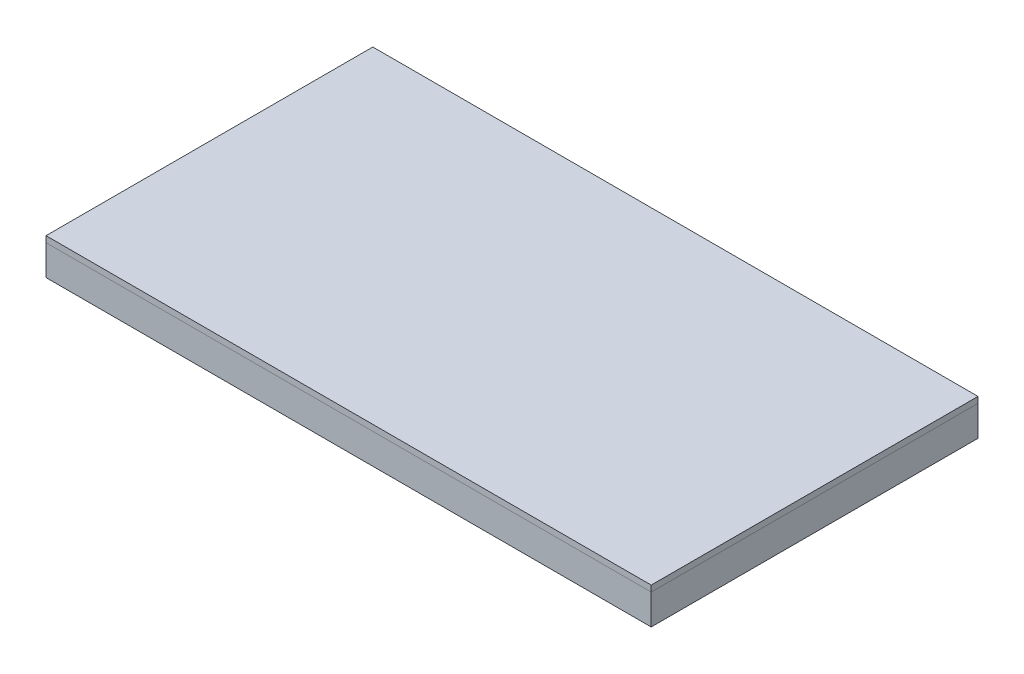
SolidWorks part; units mm, degrees
ref_plane "Front Plane" through (0, 0, 0) normal (0, 0, 1) x (1, 0, 0)
ref_plane "Top Plane" through (0, 0, 0) normal (0, 1, 0) x (1, 0, 0)
ref_plane "Right Plane" through (0, 0, 0) normal (1, 0, 0) x (0, 0, -1)
sketch "Sketch1" plane through (0, 0, 0) normal (0, 1, 0) x (1, 0, 0)
  line L1 (-500, -270) -> (500, -270)
  line L2 (-500, -270) -> (-500, 270)
  line L3 (-500, 270) -> (500, 270)
  line L4 (500, -270) -> (500, 270)
  line L5 (-500, -270) -> (500, 270) construction
  line L6 (-500, 270) -> (500, -270) construction
  line L7 (-490, -260) -> (490, -260)
  line L8 (-490, -260) -> (-490, 260)
  line L9 (-490, 260) -> (490, 260)
  line L10 (490, -260) -> (490, 260)
  line L11 (-490, -260) -> (490, 260) construction
  line L12 (-490, 260) -> (490, -260) construction
  point P0 (0, 0)
  point P6 (0, 0)
  dimension "D1" = 10
  dimension "D2" = 10
  dimension "D3" = 540
  dimension "D4" = 1000
extrude "Boss-Extrude1" add sketch "Sketch1" along normal blind 10 contours L7 L10 L9 L8 | L1 L4 L3 L2 L10 L7 L8 L9 region at (-498.8635, 0, 0) region at (0, 0, 0)
extrude "Boss-Extrude2" add sketch "Sketch1<3>" against normal blind 50 separate body
sketch "Sketch1<3>" plane through (0, 0, 0) normal (0, 1, 0) x (1, 0, 0) same geometry as "Sketch1"
